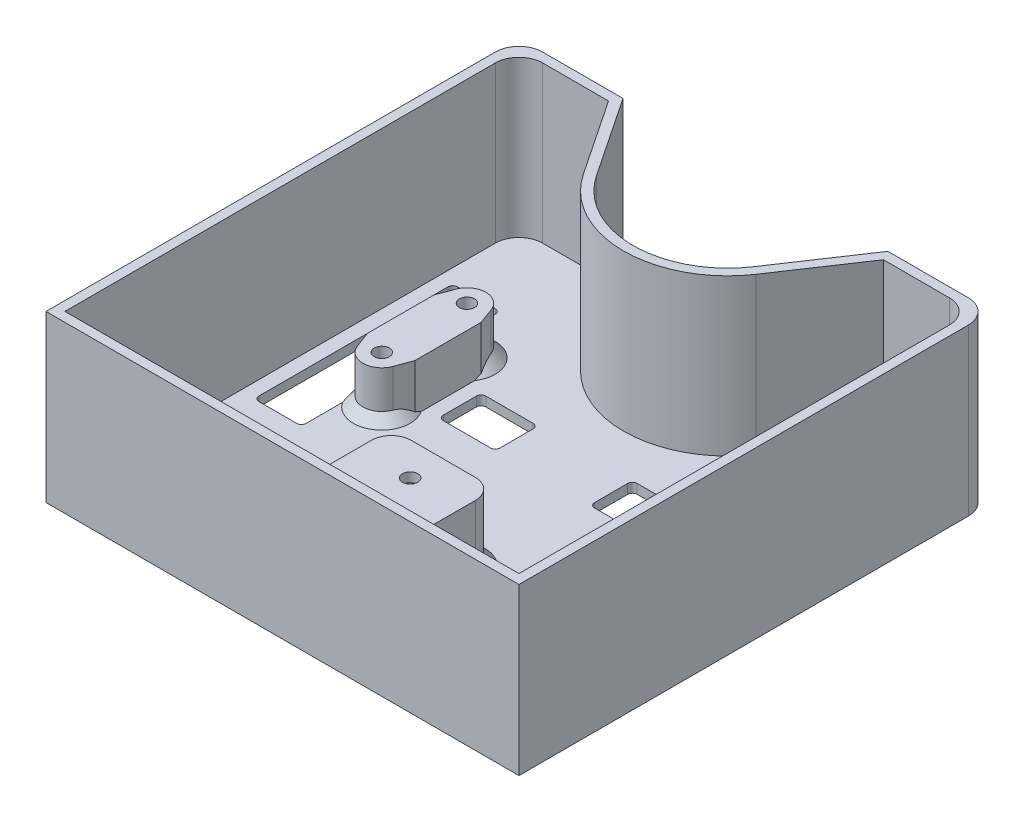
SolidWorks part; units mm, degrees
material "PVC hart"
ref_plane "Ebene vorne" through (0, 0, 0) normal (0, 0, 1) x (1, 0, 0)
ref_plane "Ebene oben" through (0, 0, 0) normal (0, 1, 0) x (1, 0, 0)
ref_plane "Ebene rechts" through (0, 0, 0) normal (1, 0, 0) x (0, 0, -1)
sketch "Grundplatte" plane through (0, 0, 0) normal (0, 1, 0) x (1, 0, 0)
  line L0 (0, 69.0751) -> (0, -94.5087) construction
  line L2 (-50, 50) -> (-50, -50)
  line L3 (-50, -50) -> (50, -50)
  line L4 (50, 50) -> (50, -50)
  line L5 (-50, 50) -> (50, -50) construction
  line L6 (-50, -50) -> (50, 50) construction
  line L7 (-50, 50) -> (-28, 50)
  line L8 (-28, 50) -> (-16.6199, 33)
  line L9 (28, 50) -> (16.6199, 33)
  line L10 (50, 50) -> (28, 50)
  arc A0 (-16.6199, 33) -> (16.6199, 33) centre (0, 44.1257) ccw
  point P0 (0, 0)
  dimension "D4" = 20
  dimension "D1" = 100
  dimension "D2" = 100
  dimension "D3" = 22
  dimension "D5" = 17
extrude "Aufsatz-Linear austragen1" add sketch "Grundplatte" along normal blind 35
shell "Wandung1" thickness 2 removed face at (0, 35, -19.6407)
sketch "Skizze1" plane through (0, 2, 0) normal (0, 1, 0) x (1, 0, 0)
  line L0 (0, 51.8201) -> (0, -55.3816) construction
  line L1 (-28, 50) -> (-50, 50) construction
  line L2 (-45, 31) -> (-35, 31)
  line L3 (-45, 31) -> (-45, -11)
  line L4 (-45, -11) -> (-35, -11)
  line L5 (-35, 31) -> (-35, -11)
  line L6 (-45, 31) -> (-35, -11) construction
  line L7 (-45, -11) -> (-35, 31) construction
  line L8 (50, 50) -> (28, 50) construction
  line L9 (35, 31) -> (45, 31)
  line L10 (35, 31) -> (35, -11)
  line L11 (35, -11) -> (45, -11)
  line L12 (45, 31) -> (45, -11)
  line L13 (35, 31) -> (45, -11) construction
  line L14 (35, -11) -> (45, 31) construction
  point P3 (-40, 10)
  point P10 (40, 10)
  dimension "D1" = 10
  dimension "D2" = 42
  dimension "D3" = 40
  dimension "D4" = 40
  dimension "D5" = 42
  dimension "D6" = 10
  dimension "D7" = 40
  dimension "D8" = 40
extrude "Schnitt-Linear austragen1" cut sketch "Skizze1" against normal up to surface (2 mm away) up to face at (0, 0, -19.6407)
sketch "Skizze2" plane through (0, 2, 0) normal (0, 1, 0) x (1, 0, 0)
  line L20 (-65.457, 10) -> (65.6069, 10) construction
  line L21 (0, 51.8201) -> (0, -54.6693) construction
  line L22 (-35, -11) -> (-35, 31) construction
  line L24 (-35, 16) -> (-35, 4)
  line L26 (-25, 16) -> (-25, 4)
  line L27 (-35, 16) -> (-25, 4) construction
  line L28 (-35, 4) -> (-25, 16) construction
  line L33 (35, 16) -> (35, 17)
  line L34 (33.7533, 20.3831) -> (35, 17)
  line L36 (-35, 16) -> (-35, 17)
  line L37 (-25, 16) -> (-25, 17)
  line L38 (-35, 4) -> (-35, 3)
  line L39 (-25, 4) -> (-25, 3)
  line L40 (-26.2467, 20.3831) -> (-25, 17)
  line L41 (-33.7533, 20.3831) -> (-35, 17)
  line L42 (-26.2467, -0.3831) -> (-25, 3)
  line L43 (-33.7533, -0.3831) -> (-35, 3)
  line L44 (26.2467, 20.3831) -> (25, 17)
  line L45 (25, 16) -> (25, 17)
  line L46 (25, 16) -> (25, 4)
  line L47 (25, 4) -> (25, 3)
  line L48 (26.2467, -0.3831) -> (25, 3)
  line L49 (33.7533, -0.3831) -> (35, 3)
  line L50 (35, 4) -> (35, 3)
  line L51 (35, 16) -> (35, 4)
  circle A4 centre (-30, 19) radius 1.6
  circle A5 centre (-30, 1) radius 1.6
  arc A6 (-26.2467, 20.3831) -> (-33.7533, 20.3831) centre (-30, 19) ccw
  arc A7 (-26.2467, -0.3831) -> (-33.7533, -0.3831) centre (-30, 1) cw
  circle A8 centre (30, 1) radius 1.6
  circle A9 centre (30, 19) radius 1.6
  arc A10 (26.2467, 20.3831) -> (33.7533, 20.3831) centre (30, 19) cw
  arc A11 (26.2467, -0.3831) -> (33.7533, -0.3831) centre (30, 1) ccw
  point P4 (-30, 10)
  point P9 (30, 10)
  dimension "D9" = 3.2
  dimension "D10" = 3.2
  dimension "D13" = 4
  dimension "D14" = 4
  dimension "D2" = 30
  dimension "D3" = 10
  dimension "D5" = 1
  dimension "D6" = 1
  dimension "D7" = 1
  dimension "D8" = 1
  dimension "D11" = 9
  dimension "D12" = 9
extrude "Aufsatz-Linear austragen2" add sketch "Skizze2" along normal blind 10
fillet "Verrundung1" radius 1 8 edges at (35, 1, -31) (45, 1, -31) (35, 1, 11) (45, 1, 11) (-35, 1, 11) (-45, 1, 11) (-45, 1, -31) (-35, 1, -31)
sketch "Skizze6" plane through (0, 12, 0) normal (0, 1, 0) x (1, 0, 0)
  circle A0 centre (-30, 19) radius 1.6
  circle A1 centre (-30, 1) radius 1.6
  circle A2 centre (30, 19) radius 1.6
  circle A3 centre (30, 1) radius 1.6
  dimension "D1" = 3.2
  dimension "D2" = 3.2
  dimension "D3" = 3.2
  dimension "D4" = 3.2
extrude "Schnitt-Linear austragen2" cut sketch "Skizze6" against normal through all
sketch "Skizze7" plane through (0, 0, 0) normal (0, -1, 0) x (1, 0, 0)
  line L0 (0, 58.5427) -> (0, -57.727) construction
  line L1 (-26.7091, -1) -> (-28.3546, 1.85)
  line L2 (-28.3546, 1.85) -> (-31.6454, 1.85)
  line L3 (-31.6454, 1.85) -> (-33.2909, -1)
  line L4 (-33.2909, -1) -> (-31.6454, -3.85)
  line L5 (-31.6454, -3.85) -> (-28.3546, -3.85)
  line L6 (-28.3546, -3.85) -> (-26.7091, -1)
  line L7 (28.3546, -21.85) -> (26.7091, -19)
  line L8 (-26.7091, -19) -> (-28.3546, -16.15)
  line L9 (-28.3546, -16.15) -> (-31.6454, -16.15)
  line L10 (-31.6454, -16.15) -> (-33.2909, -19)
  line L11 (-33.2909, -19) -> (-31.6454, -21.85)
  line L12 (-31.6454, -21.85) -> (-28.3546, -21.85)
  line L13 (-28.3546, -21.85) -> (-26.7091, -19)
  line L14 (31.6454, -21.85) -> (28.3546, -21.85)
  line L15 (33.2909, -19) -> (31.6454, -21.85)
  line L16 (31.6454, -16.15) -> (33.2909, -19)
  line L17 (28.3546, -16.15) -> (31.6454, -16.15)
  line L18 (26.7091, -19) -> (28.3546, -16.15)
  line L19 (28.3546, -3.85) -> (26.7091, -1)
  line L20 (31.6454, -3.85) -> (28.3546, -3.85)
  line L21 (33.2909, -1) -> (31.6454, -3.85)
  line L22 (31.6454, 1.85) -> (33.2909, -1)
  line L23 (28.3546, 1.85) -> (31.6454, 1.85)
  line L24 (26.7091, -1) -> (28.3546, 1.85)
  circle A0 centre (-30, -1) radius 2.85 construction
  circle A1 centre (-30, -19) radius 2.85 construction
  dimension "D1" = 5.7
  dimension "D2" = 5.7
extrude "Schnitt-Linear austragen3" cut sketch "Skizze7" against normal offset from surface (9 mm away) 3 up to face at (30, 12, -2.6)
chamfer "Fase1" distance 2 angle 45 8 edges at (34.3766, 2, -1.3084) (30, 2, 3) (34.3766, 2, -18.6916) (30, 2, -23) (-34.3766, 2, -18.6916) (-30, 2, -23) (-34.3766, 2, -1.3084) (-30, 2, 3)
sketch "Skizze8" plane through (0, 0, 0) normal (0, -1, 0) x (1, 0, 0)
  line L0 (0, 60.6503) -> (0, -60.3099) construction
  line L1 (22, -5) -> (10, -5)
  line L2 (-22, -14) -> (-10, -14)
  line L3 (-22, -14) -> (-22, -5)
  line L4 (-22, -5) -> (-10, -5)
  line L5 (-10, -14) -> (-10, -5)
  line L10 (10, -14) -> (10, -5)
  line L11 (22, -14) -> (10, -14)
  line L12 (22, -14) -> (22, -5)
  circle A0 centre (-30, -1) radius 1.6 construction
  dimension "D2" = 4
  dimension "D1" = 12
  dimension "D3" = 10
  dimension "D4" = 9
extrude "Schnitt-Linear austragen4" cut sketch "Skizze8" against normal up to surface (2 mm away) up to face at (-36.1139, 2, -10)
fillet "Verrundung2" radius 1 8 edges at (-22, 1, -14) (-22, 1, -5) (-10, 1, -5) (-10, 1, -14) (22, 1, -14) (22, 1, -5) (10, 1, -14) (10, 1, -5)
fillet "Verrundung3" radius 5 2 edges at (-50, 17.5, -50) (50, 17.5, -50)
fillet "Verrundung4" radius 5 2 edges at (48, 18.5, -48) (-48, 18.5, -48)
sketch "Skizze9" plane through (0, 0, 0) normal (0, -1, 0) x (1, 0, 0)
  line L0 (0, 55.7734) -> (0, -61.0444) construction
  line L1 (-11, -5) -> (-21, -5) construction
  line L2 (-6.8, 43) -> (6.8, 43)
  line L3 (-8, 41.8) -> (-8, 20.2)
  line L4 (-6.8, 19) -> (6.8, 19)
  line L5 (8, 41.8) -> (8, 20.2)
  line L6 (-8, 43) -> (8, 19) construction
  line L7 (-8, 19) -> (8, 43) construction
  arc A0 (6.8, 19) -> (8, 20.2) centre (6.8, 20.2) ccw
  arc A1 (-8, 20.2) -> (-6.8, 19) centre (-6.8, 20.2) ccw
  arc A2 (-6.8, 43) -> (-8, 41.8) centre (-6.8, 41.8) ccw
  arc A3 (6.8, 43) -> (8, 41.8) centre (6.8, 41.8) cw
  point P3 (0, 31)
  dimension "D4" = 1.2
  dimension "D1" = 24
  dimension "D2" = 16
  dimension "D3" = 36
extrude "Schnitt-Linear austragen5" cut sketch "Skizze9" against normal up to next
sketch "Skizze11" plane through (0, 2, 0) normal (0, 1, 0) x (1, 0, 0)
  line L25 (-6.8, -46) -> (6.8, -46)
  line L26 (-11, -20.2) -> (-11, -41.8)
  line L27 (11, -41.8) -> (11, -20.2)
  line L28 (6.8, -16) -> (-6.8, -16)
  line L29 (-6.8, -46) -> (6.8, -46)
  line L30 (-11, -20.2) -> (-11, -41.8)
  line L31 (11, -41.8) -> (11, -20.2)
  line L32 (6.8, -16) -> (-6.8, -16)
  line L62 (-8, -20.2) -> (-8, -41.8)
  line L63 (-6.8, -43) -> (6.8, -43)
  line L64 (8, -41.8) -> (8, -20.2)
  line L65 (-6.8, -19) -> (6.8, -19)
  arc A19 (6.8, -46) -> (11, -41.8) centre (6.8, -41.8) ccw
  arc A20 (-11, -41.8) -> (-6.8, -46) centre (-6.8, -41.8) ccw
  arc A21 (-6.8, -16) -> (-11, -20.2) centre (-6.8, -20.2) ccw
  arc A22 (11, -20.2) -> (6.8, -16) centre (6.8, -20.2) ccw
  arc A23 (6.8, -46) -> (11, -41.8) centre (6.8, -41.8) ccw
  arc A24 (-11, -41.8) -> (-6.8, -46) centre (-6.8, -41.8) ccw
  arc A25 (-6.8, -16) -> (-11, -20.2) centre (-6.8, -20.2) ccw
  arc A26 (11, -20.2) -> (6.8, -16) centre (6.8, -20.2) ccw
  arc A50 (-6.8, -19) -> (-8, -20.2) centre (-6.8, -20.2) ccw
  arc A51 (6.8, -19) -> (8, -20.2) centre (6.8, -20.2) cw
  arc A52 (-6.8, -43) -> (-8, -41.8) centre (-6.8, -41.8) cw
  arc A53 (6.8, -43) -> (8, -41.8) centre (6.8, -41.8) ccw
  dimension "D1" = 3
extrude "Aufsatz-Linear austragen3" add sketch "Skizze11" along normal blind 12
sketch "Skizze12" plane through (0, 14, 0) normal (0, 1, 0) x (1, 0, 0)
  line L30 (11, -41.8) -> (11, -20.2)
  line L31 (-6.8, -46) -> (6.8, -46)
  line L32 (-11, -20.2) -> (-11, -41.8)
  line L33 (6.8, -16) -> (-6.8, -16)
  line L34 (11, -41.8) -> (11, -20.2)
  line L35 (-6.8, -46) -> (6.8, -46)
  line L36 (-11, -20.2) -> (-11, -41.8)
  line L37 (6.8, -16) -> (-6.8, -16)
  arc A14 (6.8, -46) -> (11, -41.8) centre (6.8, -41.8) ccw
  arc A15 (-11, -41.8) -> (-6.8, -46) centre (-6.8, -41.8) ccw
  arc A16 (-6.8, -16) -> (-11, -20.2) centre (-6.8, -20.2) ccw
  arc A17 (11, -20.2) -> (6.8, -16) centre (6.8, -20.2) ccw
  arc A18 (6.8, -46) -> (11, -41.8) centre (6.8, -41.8) ccw
  arc A19 (-11, -41.8) -> (-6.8, -46) centre (-6.8, -41.8) ccw
  arc A20 (-6.8, -16) -> (-11, -20.2) centre (-6.8, -20.2) ccw
  arc A21 (11, -20.2) -> (6.8, -16) centre (6.8, -20.2) ccw
  dimension "D1" = 3
extrude "Aufsatz-Linear austragen4" add sketch "Skizze12" along normal blind 2
chamfer "Fase2" distance 2 angle 45 8 edges at (-11, 2, 31) (-9.7698, 2, 44.7698) (-9.7698, 2, 17.2302) (0, 2, 46) (0, 2, 16) (9.7698, 2, 44.7698) (9.7698, 2, 17.2302) (11, 2, 31)
sketch "Skizze13" plane through (0, 16, 0) normal (0, 1, 0) x (1, 0, 0)
  line L0 (0, 40.7845) -> (0, -65.4996) construction
  line L1 (-15.9895, -31) -> (16.789, -31) construction
  line L2 (6.8, -16) -> (-6.8, -16) construction
  line L3 (-6.8, -46) -> (6.8, -46) construction
  circle A0 centre (0, -23) radius 1.6
  circle A1 centre (0, -39) radius 1.6
  dimension "D1" = 3.2
  dimension "D2" = 3.2
  dimension "D3" = 16
extrude "Schnitt-Linear austragen6" cut sketch "Skizze13" along direction (0, 1, 0) on the side against the normal up to surface (2 mm away) up to face at (0, 14, 31)
